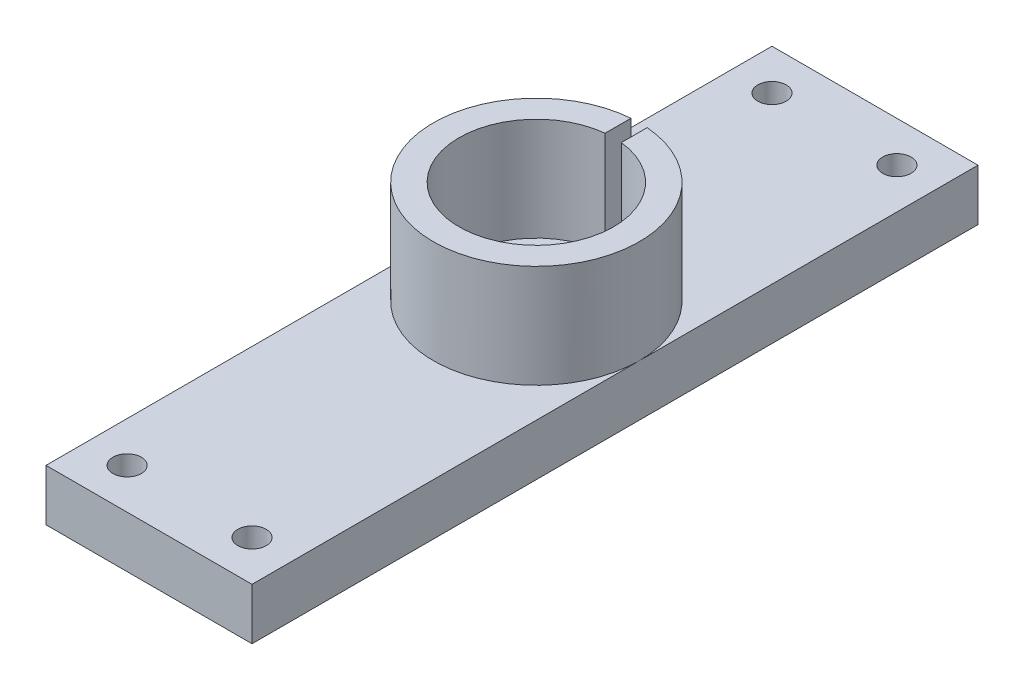
SolidWorks part; units mm, degrees
ref_plane "Front Plane" through (0, 0, 0) normal (0, 0, 1) x (1, 0, 0)
ref_plane "Top Plane" through (0, 0, 0) normal (0, 1, 0) x (1, 0, 0)
ref_plane "Right Plane" through (0, 0, 0) normal (1, 0, 0) x (0, 0, -1)
sketch "Sketch1" plane through (0, 0, 0) normal (0, 1, 0) x (1, 0, 0)
  line L1 (0, 0) -> (25.4, 0)
  line L2 (0, 0) -> (0, 89.5)
  line L3 (0, 89.5) -> (25.4, 89.5)
  line L4 (25.4, 0) -> (25.4, 89.5)
  circle A0 centre (5, 84.5) radius 1.75
  circle A1 centre (20.4, 84.5) radius 1.75
  circle A2 centre (5, 5) radius 1.75
  circle A3 centre (20.4, 5) radius 1.75
  dimension "D3" = 3.5
  dimension "D1" = 89.5
  dimension "D2" = 25.4
  dimension "D4" = 5
  dimension "D5" = 5
  dimension "D6" = 5
  dimension "D7" = 5
extrude "Boss-Extrude1" add sketch "Sketch1" along normal blind 6.35
sketch "Sketch2" plane through (0, 6.35, 0) normal (0, 1, 0) x (1, 0, 0)
  line L1 (25.4, 89.5) -> (0, 89.5) construction
  circle A0 centre (12.7, 47.75) radius 12.7
  circle A1 centre (12.7, 47.75) radius 9.525
  point P2 (12.7, 89.5)
  dimension "D1" = 41.75
  dimension "D2" = 25.4
  dimension "D3" = 19.05
extrude "Boss-Extrude2" add sketch "Sketch2" along normal blind 12.7
ref_plane "Plane1" through (0, 0, -35.05) normal (0, 0, 1) x (0, -1, 0)
sketch "Sketch5" plane through (0, 19.05, 0) normal (0, 1, 0) x (1, 0, 0)
  line L1 (11.7, 62.7043) -> (13.7, 62.7043)
  line L2 (11.7, 62.7043) -> (11.7, 54.6968)
  line L3 (11.7, 54.6968) -> (13.7, 54.6968)
  line L4 (13.7, 62.7043) -> (13.7, 54.6968)
  circle A0 centre (12.7, 47.75) radius 9.525 construction
  dimension "D1" = 1
  dimension "D2" = 2
extrude "Cut-Extrude1" cut sketch "Sketch5" against normal up to surface (12.7 mm away) up to face at (12.7, 6.35, -71.8)
sketch "Sketch6" plane through (0, 6.35, 0) normal (0, 1, 0) x (1, 0, 0)
  circle A0 centre (12.7, 47.75) radius 2.5
  dimension "D1" = 5
extrude "Cut-Extrude2" cut sketch "Sketch6" against normal blind 2.54
